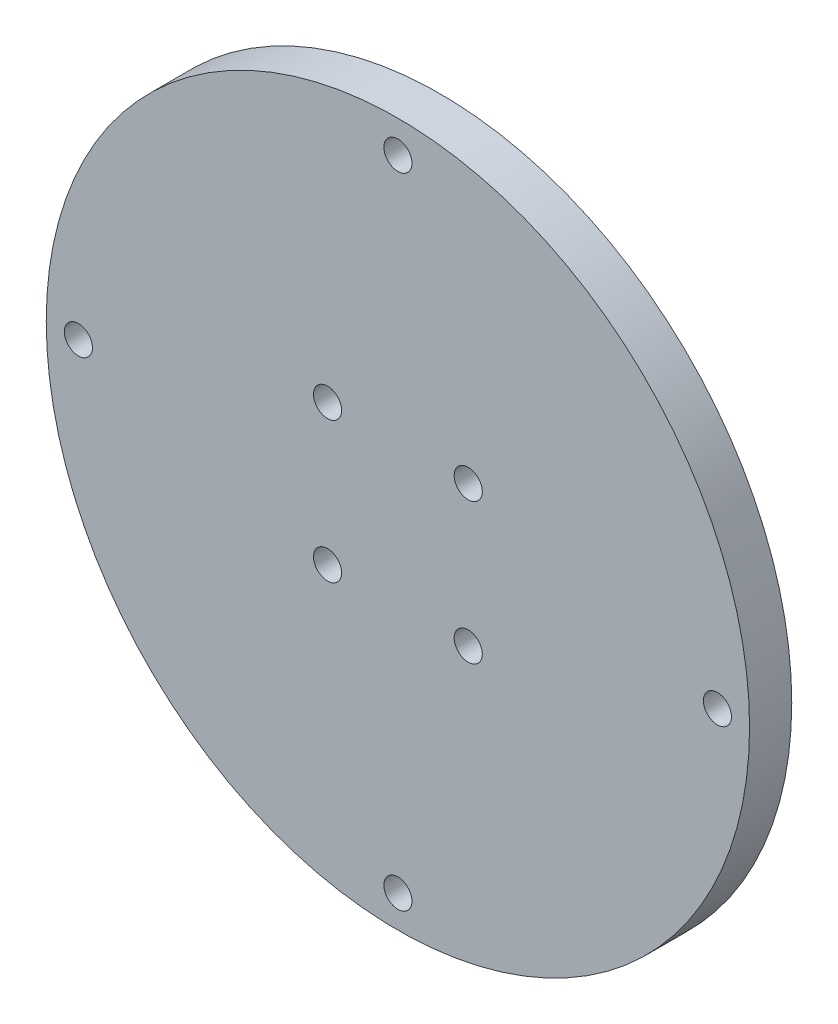
SolidWorks part; units mm, degrees
ref_plane "Front Plane" through (0, 0, 0) normal (0, 0, 1) x (1, 0, 0)
ref_plane "Top Plane" through (0, 0, 0) normal (0, 1, 0) x (1, 0, 0)
ref_plane "Right Plane" through (0, 0, 0) normal (1, 0, 0) x (0, 0, -1)
sketch "Sketch1" plane through (0, 0, 0) normal (0, 0, 1) x (1, 0, 0)
  line L1 (-5, 5) -> (5, 5)
  line L2 (-5, 5) -> (-5, -5)
  line L3 (-5, -5) -> (5, -5)
  line L4 (5, 5) -> (5, -5)
  line L5 (-5, 5) -> (5, -5) construction
  line L6 (-5, -5) -> (5, 5) construction
  circle A0 centre (0, 0) radius 25
  circle A1 centre (0, 22.714) radius 1
  circle A2 centre (22.714, 0) radius 1
  circle A3 centre (0, -22.714) radius 1
  circle A4 centre (-22.714, 0) radius 1
  circle A5 centre (-5, 5) radius 1
  circle A6 centre (5, 5) radius 1
  circle A7 centre (5, -5) radius 1
  circle A8 centre (-5, -5) radius 1
  point P5 (0, 25)
  point P15 (0, 0)
  point P16 (0, -25)
  point P17 (0, 0)
  point P18 (0, 0)
  dimension "D1" = 50
  dimension "D2" = 2
  dimension "D8" = 2
  dimension "D3" = 2.286
  dimension "D5" = 2.286
  dimension "D6" = 10
  dimension "D7" = 10
  dimension "D9" = 2
  dimension "D10" = 2
  dimension "D4" = 4
extrude "Boss-Extrude1" add sketch "Sketch1" along normal mid plane 3 contours A0 A8 L2 A5 L1 A6 L4 A7 L3 A4 A3 A2 A1 | A8 L3 A7 L4 A6 L1 A5 L2 region at (0, 0, 0) region at (-24.2929, 0, 0)
